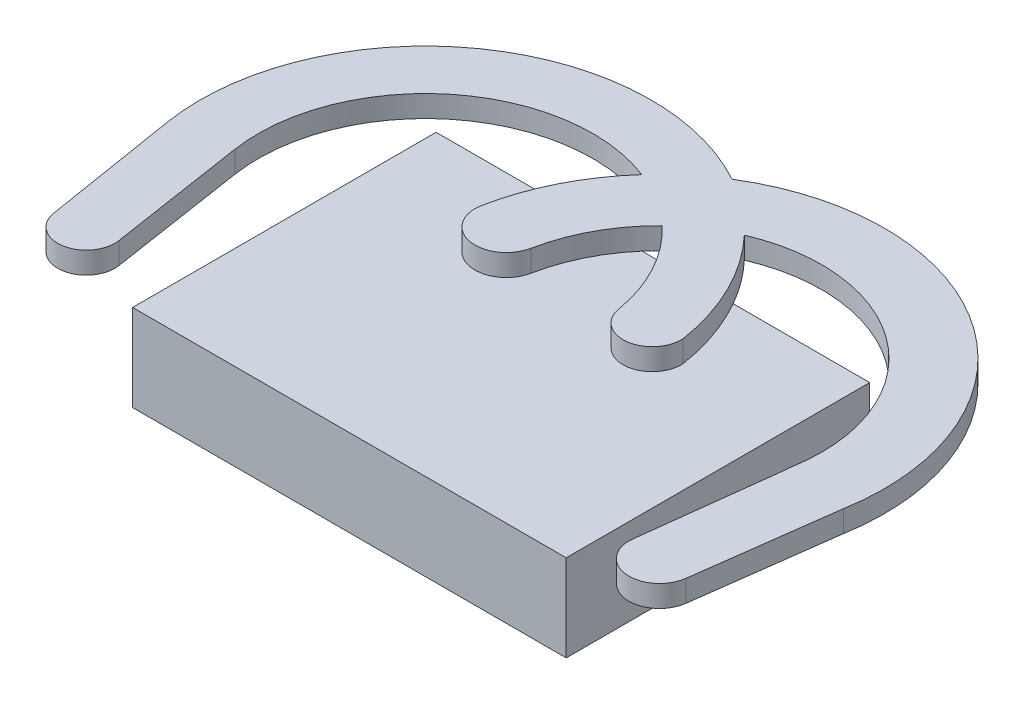
SolidWorks part; units mm, degrees
ref_plane "Front" through (0, 0, 0) normal (0, 0, 1) x (1, 0, 0)
ref_plane "Top" through (0, 0, 0) normal (0, 1, 0) x (1, 0, 0)
ref_plane "Right" through (0, 0, 0) normal (1, 0, 0) x (0, 0, -1)
sketch "Sketch2" plane through (0, 0, 0) normal (0, 0, 1) x (1, 0, 0)
  line L1 (-53.3576, 8.3344) -> (10.1424, 8.3344)
  line L2 (-53.3576, 8.3344) -> (-53.3576, -4.3656)
  line L3 (-53.3576, -4.3656) -> (10.1424, -4.3656)
  line L4 (10.1424, 8.3344) -> (10.1424, -4.3656)
  dimension "D1" = 12.7
  dimension "D2" = 63.5
extrude "Boss-Extrude1" add sketch "Sketch2" along normal blind 44.45
sketch "Sketch3" plane through (0, 8.3344, 0) normal (0, 1, 0) x (1, 0, 0)
  line L0 (-53.3576, -44.45) -> (-53.3576, 0) construction
  line L1 (10.1424, -44.45) -> (10.1424, 0) construction
  line L2 (10.1424, -44.45) -> (-53.3576, -44.45) construction
  line L3 (27.3842, -21.0966) -> (24.6862, -41.4716)
  line L4 (18.2346, -20.32) -> (15.8108, -40.2963)
  arc A0 (-33.0376, -10.0285) -> (22.8424, -20.32) centre (-5.1634, -15.5316) cw construction
  arc A1 (27.3842, -21.0966) -> (-37.5582, -9.1361) centre (-5.1634, -15.5316) ccw
  arc A2 (18.3005, -19.5434) -> (-28.5171, -10.921) centre (-5.1634, -15.5316) ccw
  arc A3 (18.3005, -19.5434) -> (18.2346, -20.32) centre (22.8424, -20.32) ccw
  arc A4 (-37.5582, -9.1361) -> (-28.5171, -10.921) centre (-33.0376, -10.0285) ccw
  arc A5 (24.6862, -41.4716) -> (15.8108, -40.2963) centre (20.2485, -40.8839) cw
  point P0 (-33.0376, -10.0285)
  point P3 (-10.1776, -6.7463)
  point P9 (-0.0173, 12.4107)
  dimension "D3" = 33.02
  dimension "D1" = 20.32
  dimension "D2" = 20.32
  dimension "D4" = 12.7
  dimension "D5" = 24.13
extrude "Boss-Extrude2" add sketch "Sketch3" along normal blind 3.175 contours A2 A4 A1 L3 A5 L4 A3
sketch "Sketch6" plane through (0, 8.3344, 0) normal (0, 1, 0) x (1, 0, 0)
  line L0 (10.1424, -44.45) -> (10.1424, 0) construction
  line L1 (-5.1634, 17.4884) -> (50.613, 17.4884)
  line L2 (50.613, 17.4884) -> (-68.802, 17.4884)
  line L3 (-71.1342, -21.6551) -> (-67.9142, -41.4691)
  line L4 (-62.7606, -20.0837) -> (-59.6716, -40.1654)
  line L5 (10.1424, -44.45) -> (-53.3576, -44.45) construction
  arc A0 (-10.1776, -11.5329) -> (-64.0419, -29.6832) centre (-38.5418, -16.3584) ccw construction
  arc A1 (-5.9187, -11.2543) -> (-71.1342, -21.6551) centre (-38.5418, -16.3584) ccw
  arc A2 (-14.3869, -12.2388) -> (-62.7606, -20.0837) centre (-38.5418, -16.3584) ccw
  arc A3 (-14.3869, -12.2388) -> (-5.9187, -11.2543) centre (-10.1776, -11.5329) ccw
  arc A4 (-59.6716, -40.1654) -> (-67.9142, -41.4691) centre (-63.7957, -40.7998) cw
  arc A5 (27.3842, -21.0966) -> (-37.5582, -9.1361) centre (-5.1634, -15.5316) ccw construction
  point P0 (-10.1776, -11.5329)
  point P6 (-47.7882, 11.4219)
  dimension "D2" = 33.02
  dimension "D3" = 20.0739
  dimension "D1" = 20.32
  dimension "D4" = 14.7668
extrude "Boss-Extrude3" add sketch "Sketch2<2>" along normal blind 3.175
sketch "Sketch2<2>" plane through (0, 0, 0) normal (0, 0, 1) x (1, 0, 0) same geometry as "Sketch2"
extrude "Boss-Extrude4" add sketch "Sketch6" along normal blind 3.175 contours A1 L3 A4 L4 A2 A3
